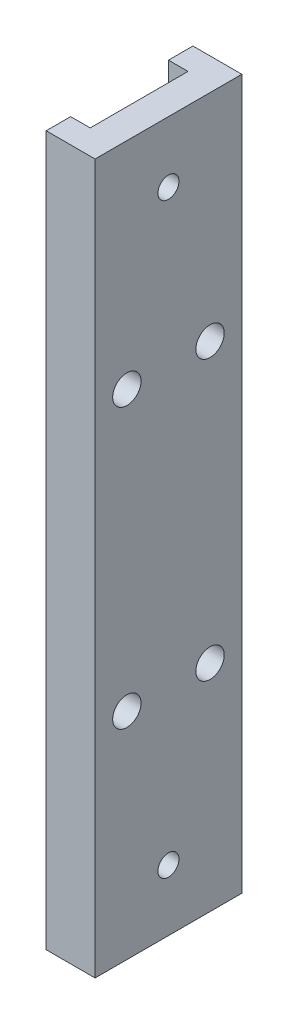
SolidWorks part; units mm, degrees
ref_plane "Front Plane" through (0, 0, 0) normal (0, 0, 1) x (1, 0, 0)
ref_plane "Top Plane" through (0, 0, 0) normal (0, 1, 0) x (1, 0, 0)
ref_plane "Right Plane" through (0, 0, 0) normal (1, 0, 0) x (0, 0, -1)
ref_plane "Plane1" through (0, 260, 0) normal (0, -1, 0) x (-1, 0, 0)
sketch "Sketch1" plane through (0, 260, 0) normal (0, -1, 0) x (-1, 0, 0)
  line L0 (71.5, -127.5) -> (61.5, -127.5)
  line L1 (61.5, -127.5) -> (61.5, -97.5)
  line L2 (61.5, -97.5) -> (71.5, -97.5)
  line L3 (71.5, -97.5) -> (71.5, -102.5)
  line L4 (71.5, -102.5) -> (67.5, -102.5)
  line L5 (67.5, -102.5) -> (67.5, -122.5)
  line L6 (67.5, -122.5) -> (71.5, -122.5)
  line L7 (71.5, -122.5) -> (71.5, -127.5)
  line L8 (68.9986, -122.5) -> (74.3631, -122.5) construction
  line L9 (68.9986, -102.5) -> (74.3631, -102.5) construction
  line L10 (67.5, -115.6369) -> (67.5, -121.0014) construction
  dimension "D1" = 5
  dimension "D2" = 10
  dimension "D3" = 6
extrude "Boss-Extrude1" add sketch "Sketch1" along normal blind 145
sketch "Sketch5" plane through (-61.5, 0, 0) normal (1, 0, 0) x (0, 0, -1)
  line L0 (-97.5, 260) -> (-127.5, 260) construction
  line L1 (-121, 159) -> (-104, 159) construction
  line L2 (-121, 159) -> (-121, 216) construction
  line L3 (-121, 216) -> (-104, 216) construction
  line L4 (-104, 159) -> (-104, 216) construction
  line L5 (-121, 159) -> (-104, 216) construction
  line L6 (-121, 216) -> (-104, 159) construction
  line L7 (-97.5, 115) -> (-97.5, 260) construction
  point P0 (-112.5, 187.5)
  point P5 (0, 0)
  point P8 (-112.5, 260)
  point P11 (-97.5, 187.5)
  dimension "D1" = 17
  dimension "D2" = 57
hole_wizard "M4 Clearance Hole1" positions "Sketch2" profile "Sketch4" hole size "M4" standard "ISO" end condition through all
sketch "Sketch2" plane through (-61.5, 0, 0) normal (1, 0, 0) x (0, 0, -1)
  line L0 (-112.5, 247.5) -> (-112.5, 127.5) construction
  line L2 (-97.5, 260) -> (-127.5, 260) construction
  line L4 (-112.5, 247.5) -> (-112.5, 260) construction
  line L7 (-112.5, 127.5) -> (-112.5, 115) construction
  line L8 (-97.5, 115) -> (-127.5, 115) construction
  point P1 (-112.5, 247.5)
  point P2 (-112.5, 127.5)
  point P7 (-112.5, 260)
  dimension "D1" = 120
sketch "Sketch4" plane through (-61.5, 247.5, 112.5) normal (0, 1, 0) x (0, 0, -1)
  line L0 (0, 0) -> (0, 10)
  line L1 (0, 10) -> (2.15, 10)
  line L2 (2.15, 10) -> (2.15, 0)
  line L5 (2.15, 0) -> (0, 0)
  line L11 (0, -6.35) -> (0, 107.95) construction
  dimension "Thru Hole Dia." = 4.3
  dimension "Thru Hole Depth" = 10
hole_wizard "Hole1" positions "Sketch6" profile "Sketch7" legacy
sketch "Sketch6" plane through (-61.5, 0, 0) normal (1, 0, 0) x (0, 0, -1)
  point P0 (-104, 216)
  point P3 (-121, 216)
  point P6 (-104, 159)
  point P9 (-121, 159)
sketch "Sketch7" plane through (-61.5, 216, 104) normal (0, 1, 0) x (0, 0, -1)
  line L0 (0, 0) -> (0, 6)
  line L1 (0, 6) -> (2.9, 6)
  line L2 (2.9, 6) -> (2.9, 0)
  line L3 (2.9, 0) -> (0, 0)
  line L4 (0, 110) -> (0, -10) construction
  dimension "Diameter" = 5.8
  dimension "Depth" = 6
